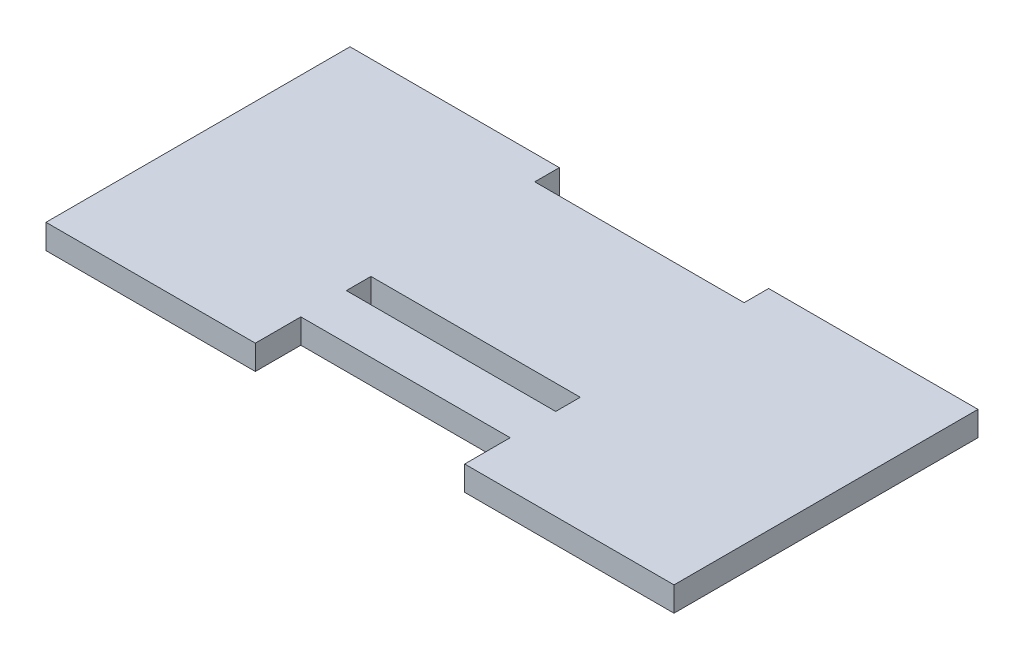
SolidWorks part; units mm, degrees
ref_plane "Front Plane" through (0, 0, 0) normal (0, 0, 1) x (1, 0, 0)
ref_plane "Top Plane" through (0, 0, 0) normal (0, 1, 0) x (1, 0, 0)
ref_plane "Right Plane" through (0, 0, 0) normal (1, 0, 0) x (0, 0, -1)
sketch "Sketch1" plane through (0, 0, 0) normal (0, 1, 0) x (1, 0, 0)
  line L1 (-34.5, 16.7) -> (-11.5, 16.7)
  line L2 (-34.5, 16.7) -> (-34.5, -16.7)
  line L3 (-34.5, -16.7) -> (-11.5, -16.7)
  line L4 (34.5, 16.7) -> (34.5, -16.7)
  line L5 (-11.5, -6.7) -> (11.5, -6.7)
  line L7 (-11.5, 14) -> (11.5, 14)
  line L9 (11.5, 16.7) -> (34.5, 16.7)
  line L10 (-11.5, -4) -> (11.5, -4)
  line L13 (-11.5, -11.7) -> (11.5, -11.7)
  line L16 (-11.5, 16.7) -> (-11.5, 14)
  line L17 (11.5, 16.7) -> (11.5, 14)
  line L18 (-11.5, -4) -> (-11.5, -6.7)
  line L19 (11.5, -4) -> (11.5, -6.7)
  line L20 (11.5, -11.7) -> (11.5, -16.7)
  line L21 (-11.5, -11.7) -> (-11.5, -16.7)
  line L22 (11.5, -16.7) -> (34.5, -16.7)
  point P0 (0, 0)
  dimension "D1" = 69
  dimension "D2" = 33.4
extrude "Boss-Extrude1" add sketch "Sketch1" along normal blind 2.7
